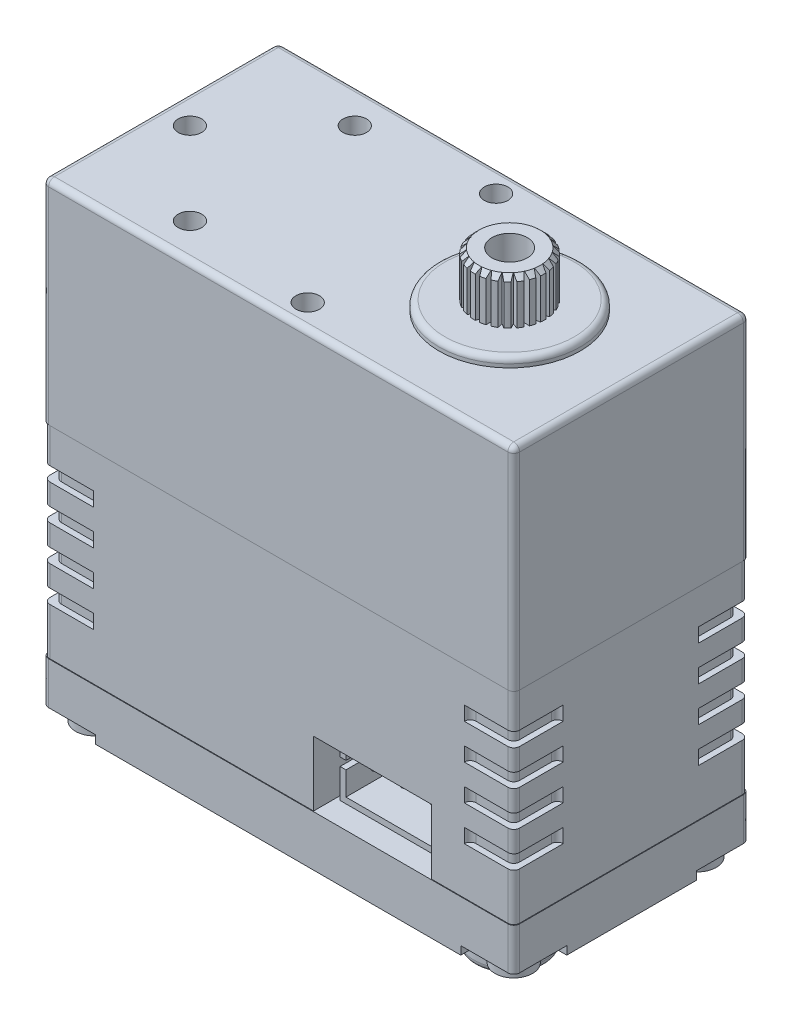
SolidWorks part; units mm, degrees
ref_plane "前视基准面" through (0, 0, 0) normal (0, 0, 1) x (1, 0, 0)
ref_plane "上视基准面" through (0, 0, 0) normal (0, 1, 0) x (1, 0, 0)
ref_plane "右视基准面" through (0, 0, 0) normal (1, 0, 0) x (0, 0, -1)
sketch "草图1" plane through (0, 0, 0) normal (0, 1, 0) x (1, 0, 0)
  line L1 (20, -10) -> (-20, -10)
  line L2 (20, -10) -> (20, 10)
  line L3 (20, 10) -> (-20, 10)
  line L4 (-20, -10) -> (-20, 10)
  line L5 (20, -10) -> (-20, 10) construction
  line L6 (20, 10) -> (-20, -10) construction
  point P0 (0, 0)
  dimension "D1" = 20
  dimension "D2" = 40
extrude "凸台-拉伸1" add sketch "草图1" along normal blind 40
sketch "草图2" plane through (0, 0, 10) normal (0, 0, 1) x (1, 0, 0)
  line L0 (-20, 40) -> (-20, 0) construction
  line L1 (-20, 22) -> (20, 22)
  line L2 (-20, 22) -> (-20, 4.8)
  line L3 (-20, 4.8) -> (20, 4.8)
  line L4 (20, 22) -> (20, 4.8)
  line L5 (20, 40) -> (20, 0) construction
  line L6 (-20, 40) -> (20, 40) construction
  dimension "D1" = 17.2
  dimension "D2" = 18
extrude "切除-拉伸1" cut sketch "草图2" against normal blind 0.05
sketch "草图3" plane through (20, 0, 0) normal (1, 0, 0) x (0, 0, -1)
  line L0 (10, 40) -> (10, 0) construction
  line L1 (-9.95, 22) -> (10, 22)
  line L2 (-9.95, 22) -> (-9.95, 4.8)
  line L3 (-9.95, 4.8) -> (10, 4.8)
  line L4 (10, 22) -> (10, 4.8)
  dimension "D1" = 17.2
extrude "切除-拉伸2" cut sketch "草图3" against normal blind 0.05
sketch "草图4" plane through (0, 0, -10) normal (0, 0, -1) x (-1, 0, 0)
  line L0 (20, 40) -> (20, 0) construction
  line L1 (-19.95, 22) -> (20, 22)
  line L2 (-19.95, 22) -> (-19.95, 4.8)
  line L3 (-19.95, 4.8) -> (20, 4.8)
  line L4 (20, 22) -> (20, 4.8)
  dimension "D1" = 17.2
extrude "切除-拉伸3" cut sketch "草图4" against normal blind 0.05
sketch "草图5" plane through (-20, 0, 0) normal (-1, 0, 0) x (0, 0, 1)
  line L1 (-9.95, 22) -> (10, 22)
  line L2 (-9.95, 22) -> (-9.95, 4.8)
  line L3 (-9.95, 4.8) -> (10, 4.8)
  line L4 (10, 22) -> (10, 4.8)
extrude "切除-拉伸4" cut sketch "草图5" against normal blind 0.05
sketch "草图6" plane through (0, 0, -9.95) normal (0, 0, -1) x (-1, 0, 0)
  line L0 (19.95, 22) -> (19.95, 4.8) construction
  line L1 (15.75, 19) -> (19.95, 19)
  line L2 (15.75, 19) -> (15.75, 17.8)
  line L3 (15.75, 17.8) -> (19.95, 17.8)
  line L4 (19.95, 19) -> (19.95, 17.8)
  line L5 (0, 22) -> (0, 4.8) construction
  line L6 (20, 22) -> (-20, 22) construction
  line L7 (20, 4.8) -> (-20, 4.8) construction
  line L8 (19.95, 22) -> (-19.95, 22) construction
  line L9 (15.75, 16) -> (15.75, 14.8)
  line L10 (15.75, 16) -> (19.95, 16)
  line L11 (19.95, 16) -> (19.95, 14.8)
  line L12 (15.75, 14.8) -> (19.95, 14.8)
  line L13 (15.75, 13) -> (15.75, 11.8)
  line L14 (15.75, 13) -> (19.95, 13)
  line L15 (19.95, 13) -> (19.95, 11.8)
  line L16 (15.75, 11.8) -> (19.95, 11.8)
  line L17 (15.75, 10) -> (15.75, 8.8)
  line L18 (15.75, 10) -> (19.95, 10)
  line L19 (19.95, 10) -> (19.95, 8.8)
  line L20 (15.75, 8.8) -> (19.95, 8.8)
  line L21 (-15.75, 10) -> (-19.95, 10)
  line L22 (-19.95, 10) -> (-19.95, 8.8)
  line L23 (-15.75, 8.8) -> (-19.95, 8.8)
  line L24 (-15.75, 10) -> (-15.75, 8.8)
  line L25 (-15.75, 13) -> (-19.95, 13)
  line L26 (-19.95, 13) -> (-19.95, 11.8)
  line L27 (-15.75, 11.8) -> (-19.95, 11.8)
  line L28 (-15.75, 13) -> (-15.75, 11.8)
  line L29 (-15.75, 16) -> (-19.95, 16)
  line L30 (-19.95, 16) -> (-19.95, 14.8)
  line L31 (-15.75, 14.8) -> (-19.95, 14.8)
  line L32 (-15.75, 16) -> (-15.75, 14.8)
  line L33 (-15.75, 17.8) -> (-19.95, 17.8)
  line L34 (-19.95, 19) -> (-19.95, 17.8)
  line L35 (-15.75, 19) -> (-19.95, 19)
  line L36 (-15.75, 19) -> (-15.75, 17.8)
  dimension "D1" = 3
  dimension "D2" = 1.2
  dimension "D3" = 4.2
  dimension "D4" = 4
extrude "切除-拉伸5" cut sketch "草图6" against normal blind 0.5
sketch "草图7" plane through (-19.95, 0, 0) normal (-1, 0, 0) x (0, 0, 1)
  line L0 (-9.95, 16) -> (-9.95, 14.8)
  line L1 (-9.95, 19) -> (-5.75, 19)
  line L2 (-9.95, 19) -> (-9.95, 17.8)
  line L3 (-9.95, 17.8) -> (-5.75, 17.8)
  line L4 (-5.75, 19) -> (-5.75, 17.8)
  line L5 (-9.95, 16) -> (-5.75, 16)
  line L6 (-5.75, 16) -> (-5.75, 14.8)
  line L7 (-9.95, 14.8) -> (-5.75, 14.8)
  line L8 (-9.95, 13) -> (-9.95, 11.8)
  line L9 (-9.95, 13) -> (-5.75, 13)
  line L10 (-5.75, 13) -> (-5.75, 11.8)
  line L11 (-9.95, 11.8) -> (-5.75, 11.8)
  line L12 (-9.95, 10) -> (-9.95, 8.8)
  line L13 (-9.95, 10) -> (-5.75, 10)
  line L14 (-5.75, 10) -> (-5.75, 8.8)
  line L15 (-9.95, 8.8) -> (-5.75, 8.8)
  line L16 (0, 22) -> (0, 4.8) construction
  line L17 (-10, 22) -> (10, 22) construction
  line L18 (-10, 4.8) -> (10, 4.8) construction
  line L19 (9.95, 10) -> (5.75, 10)
  line L20 (5.75, 10) -> (5.75, 8.8)
  line L21 (9.95, 8.8) -> (5.75, 8.8)
  line L22 (9.95, 10) -> (9.95, 8.8)
  line L23 (9.95, 13) -> (5.75, 13)
  line L24 (5.75, 13) -> (5.75, 11.8)
  line L25 (9.95, 11.8) -> (5.75, 11.8)
  line L26 (9.95, 13) -> (9.95, 11.8)
  line L27 (9.95, 16) -> (5.75, 16)
  line L28 (5.75, 16) -> (5.75, 14.8)
  line L29 (9.95, 14.8) -> (5.75, 14.8)
  line L30 (9.95, 16) -> (9.95, 14.8)
  line L31 (9.95, 17.8) -> (5.75, 17.8)
  line L32 (5.75, 19) -> (5.75, 17.8)
  line L33 (9.95, 19) -> (5.75, 19)
  line L34 (9.95, 19) -> (9.95, 17.8)
  dimension "D1" = 4.2
  dimension "D2" = 1.2
  dimension "D3" = 4
extrude "切除-拉伸6" cut sketch "草图7" against normal blind 0.5
sketch "草图8" plane through (0, 0, 9.95) normal (0, 0, 1) x (1, 0, 0)
  line L0 (0, 22) -> (0, 4.8) construction
  line L1 (-19.95, 19) -> (-15.75, 19)
  line L2 (-19.95, 19) -> (-19.95, 17.8)
  line L3 (-19.95, 17.8) -> (-15.75, 17.8)
  line L4 (-15.75, 19) -> (-15.75, 17.8)
  line L5 (20, 22) -> (-20, 22) construction
  line L6 (-20, 4.8) -> (20, 4.8) construction
  line L7 (-19.95, 16) -> (-19.95, 14.8)
  line L8 (-19.95, 16) -> (-15.75, 16)
  line L9 (-15.75, 16) -> (-15.75, 14.8)
  line L10 (-19.95, 14.8) -> (-15.75, 14.8)
  line L11 (-19.95, 13) -> (-19.95, 11.8)
  line L12 (-19.95, 13) -> (-15.75, 13)
  line L13 (-15.75, 13) -> (-15.75, 11.8)
  line L14 (-19.95, 11.8) -> (-15.75, 11.8)
  line L15 (-19.95, 10) -> (-19.95, 8.8)
  line L16 (-19.95, 10) -> (-15.75, 10)
  line L17 (-15.75, 10) -> (-15.75, 8.8)
  line L18 (-19.95, 8.8) -> (-15.75, 8.8)
  line L19 (19.95, 10) -> (15.75, 10)
  line L20 (15.75, 10) -> (15.75, 8.8)
  line L21 (19.95, 8.8) -> (15.75, 8.8)
  line L22 (19.95, 10) -> (19.95, 8.8)
  line L23 (19.95, 13) -> (15.75, 13)
  line L24 (15.75, 13) -> (15.75, 11.8)
  line L25 (19.95, 11.8) -> (15.75, 11.8)
  line L26 (19.95, 13) -> (19.95, 11.8)
  line L27 (19.95, 16) -> (15.75, 16)
  line L28 (15.75, 16) -> (15.75, 14.8)
  line L29 (19.95, 14.8) -> (15.75, 14.8)
  line L30 (19.95, 16) -> (19.95, 14.8)
  line L31 (19.95, 17.8) -> (15.75, 17.8)
  line L32 (15.75, 19) -> (15.75, 17.8)
  line L33 (19.95, 19) -> (15.75, 19)
  line L34 (19.95, 19) -> (19.95, 17.8)
  dimension "D1" = 1.2
  dimension "D2" = 4.2
  dimension "D3" = 4
extrude "切除-拉伸7" cut sketch "草图8" against normal blind 0.5
sketch "草图9" plane through (19.95, 0, 0) normal (1, 0, 0) x (0, 0, -1)
  line L0 (0, 22) -> (0, 4.8) construction
  line L1 (-9.95, 19) -> (-5.75, 19)
  line L2 (-9.95, 19) -> (-9.95, 17.8)
  line L3 (-9.95, 17.8) -> (-5.75, 17.8)
  line L4 (-5.75, 19) -> (-5.75, 17.8)
  line L5 (10, 22) -> (-10, 22) construction
  line L6 (10, 4.8) -> (-10, 4.8) construction
  line L7 (-9.95, 16) -> (-9.95, 14.8)
  line L8 (-9.95, 16) -> (-5.75, 16)
  line L9 (-5.75, 16) -> (-5.75, 14.8)
  line L10 (-9.95, 14.8) -> (-5.75, 14.8)
  line L11 (-9.95, 13) -> (-9.95, 11.8)
  line L12 (-9.95, 13) -> (-5.75, 13)
  line L13 (-5.75, 13) -> (-5.75, 11.8)
  line L14 (-9.95, 11.8) -> (-5.75, 11.8)
  line L15 (-9.95, 10) -> (-9.95, 8.8)
  line L16 (-9.95, 10) -> (-5.75, 10)
  line L17 (-5.75, 10) -> (-5.75, 8.8)
  line L18 (-9.95, 8.8) -> (-5.75, 8.8)
  line L19 (9.95, 10) -> (5.75, 10)
  line L20 (5.75, 10) -> (5.75, 8.8)
  line L21 (9.95, 8.8) -> (5.75, 8.8)
  line L22 (9.95, 10) -> (9.95, 8.8)
  line L23 (9.95, 13) -> (5.75, 13)
  line L24 (5.75, 13) -> (5.75, 11.8)
  line L25 (9.95, 11.8) -> (5.75, 11.8)
  line L26 (9.95, 13) -> (9.95, 11.8)
  line L27 (9.95, 16) -> (5.75, 16)
  line L28 (5.75, 16) -> (5.75, 14.8)
  line L29 (9.95, 14.8) -> (5.75, 14.8)
  line L30 (9.95, 16) -> (9.95, 14.8)
  line L31 (9.95, 17.8) -> (5.75, 17.8)
  line L32 (5.75, 19) -> (5.75, 17.8)
  line L33 (9.95, 19) -> (5.75, 19)
  line L34 (9.95, 19) -> (9.95, 17.8)
  dimension "D1" = 1.2
  dimension "D2" = 4.2
  dimension "D3" = 4
extrude "切除-拉伸8" cut sketch "草图9" against normal blind 0.5
sketch "草图10" plane through (0, 0, 0) normal (0, -1, 0) x (1, 0, 0)
  line L0 (-20, 0) -> (20, 0) construction
  line L1 (-20, -10) -> (-20, 10) construction
  line L2 (20, 10) -> (20, -10) construction
  line L3 (0, 10) -> (0, -10) construction
  line L4 (-20, 10) -> (20, 10) construction
  line L5 (20, -10) -> (-20, -10) construction
  line L6 (-20, -5.5) -> (-19, -5.5)
  line L7 (-20, 10) -> (-15.5, 10)
  line L8 (-20, 10) -> (-20, 5.5)
  line L9 (-20, 5.5) -> (-19, 5.5)
  line L10 (-15.5, 10) -> (-15.5, 9)
  line L11 (-15.5, -10) -> (-15.5, -9)
  line L12 (-20, -10) -> (-15.5, -10)
  line L13 (-20, -10) -> (-20, -5.5)
  line L14 (20, -10) -> (20, -5.5)
  line L15 (20, -10) -> (15.5, -10)
  line L16 (15.5, -10) -> (15.5, -9)
  line L17 (20, -5.5) -> (19, -5.5)
  line L18 (20, 5.5) -> (19, 5.5)
  line L19 (15.5, 10) -> (15.5, 9)
  line L20 (20, 10) -> (15.5, 10)
  line L21 (20, 10) -> (20, 5.5)
  arc A0 (-19, 5.5) -> (-15.5, 9) centre (-19, 9) ccw
  arc A1 (-19, -5.5) -> (-15.5, -9) centre (-19, -9) cw
  arc A2 (19, -5.5) -> (15.5, -9) centre (19, -9) ccw
  arc A3 (19, 5.5) -> (15.5, 9) centre (19, 9) cw
  dimension "D3" = 3.5
  dimension "D1" = 4.5
  dimension "D2" = 4.5
extrude "切除-拉伸9" cut sketch "草图10" against normal blind 1.2
fillet "圆角1" radius 0.5 80 edges at (20, 3, 10) (19.95, 6.8, 9.95) (19.45, 9.4, 9.45) (19.95, 10.9, 9.95) (19.45, 12.4, 9.45) (19.95, 13.9, 9.95) (19.45, 15.4, 9.45) (19.95, 16.9, 9.95) (19.45, 18.4, 9.45) (20, 31, 10) (19.95, 20.5, 9.95) (-20, 3, 10) (-19.95, 6.8, 9.95) (-19.45, 9.4, 9.45) (-19.95, 10.9, 9.95) (-19.45, 12.4, 9.45) (-19.95, 13.9, 9.95) (-19.45, 15.4, 9.45) (-19.95, 16.9, 9.95) (-19.45, 18.4, 9.45) (-20, 31, 10) (-19.95, 20.5, 9.95) (-20, 3, -10) (-19.95, 6.8, -9.95) (-19.45, 9.4, -9.45) (-19.95, 10.9, -9.95) (-19.45, 12.4, -9.45) (-19.95, 13.9, -9.95) (-19.45, 15.4, -9.45) (-19.95, 16.9, -9.95) (-19.45, 18.4, -9.45) (-20, 31, -10) (-19.95, 20.5, -9.95) (-20, 40, 0) (0, 40, 10) (20, 40, 0) (20, 3, -10) (19.95, 6.8, -9.95) (19.45, 9.4, -9.45) (19.95, 10.9, -9.95) (19.45, 12.4, -9.45) (19.95, 13.9, -9.95) (19.95, 16.9, -9.95) (19.45, 15.4, -9.45) (19.45, 18.4, -9.45) (20, 31, -10) (19.95, 20.5, -9.95) (0, 40, -10) (19.45, 9.4, 5.75) (19.45, 12.4, 5.75) (19.45, 15.4, 5.75) (19.45, 18.4, 5.75) (15.75, 9.4, 9.45) (15.75, 12.4, 9.45) (15.75, 15.4, 9.45) (15.75, 18.4, 9.45) (19.45, 18.4, -5.75) (19.45, 15.4, -5.75) (19.45, 12.4, -5.75) (19.45, 9.4, -5.75) (15.75, 9.4, -9.45) (15.75, 12.4, -9.45) (15.75, 15.4, -9.45) (15.75, 18.4, -9.45) (-15.75, 9.4, -9.45) (-15.75, 12.4, -9.45) (-15.75, 15.4, -9.45) (-15.75, 18.4, -9.45) (-19.45, 9.4, -5.75) (-19.45, 12.4, -5.75) (-19.45, 15.4, -5.75) (-19.45, 18.4, -5.75) (-15.75, 9.4, 9.45) (-15.75, 12.4, 9.45) (-15.75, 15.4, 9.45) (-15.75, 18.4, 9.45) (-19.45, 9.4, 5.75) (-19.45, 12.4, 5.75) (-19.45, 15.4, 5.75) (-19.45, 18.4, 5.75)
chamfer "倒角1" distance 0.5 angle 45 16 edges at (19.5, 0, -5.5) (16.5251, 0, -6.5251) (15.5, 0, -9.5) (0, 0, -10) (-15.5, 0, -9.5) (-16.5251, 0, -6.5251) (-19.5, 0, -5.5) (-20, 0, 0) (-19.5, 0, 5.5) (-16.5251, 0, 6.5251) (-15.5, 0, 9.5) (0, 0, 10) (15.5, 0, 9.5) (16.5251, 0, 6.5251) (19.5, 0, 5.5) (20, 0, 0)
sketch "草图12" plane through (0, 1.2, 0) normal (0, -1, 0) x (1, 0, 0)
  line L0 (-15.5, 10) -> (-19.5, 10) construction
  line L1 (-20, 9.5) -> (-20, 5.5) construction
  line L2 (-20, 0) -> (20, 0) construction
  line L3 (-20, -5.5) -> (-20, 5.5) construction
  line L4 (20, 5.5) -> (20, -5.5) construction
  line L5 (0, 10) -> (0, -10) construction
  line L6 (-15.5, 10) -> (15.5, 10) construction
  line L7 (15.5, -10) -> (-15.5, -10) construction
  circle A0 centre (-17.8, 7.8) radius 1.6
  circle A2 centre (-17.8, -7.8) radius 1.6
  circle A3 centre (17.8, -7.8) radius 1.6
  circle A4 centre (17.8, 7.8) radius 1.6
  dimension "D3" = 3.2
  dimension "D1" = 2.2
  dimension "D2" = 2.2
extrude "凸台-拉伸2" add sketch "草图12" along normal blind 1.2
sketch "草图13" plane through (0, 0, 0) normal (0, -1, 0) x (1, 0, 0)
  line L0 (-20, 0) -> (20, 0) construction
  line L1 (-20, -5.5) -> (-20, 5.5) construction
  line L2 (20, 5.5) -> (20, -5.5) construction
  line L3 (0, 10) -> (0, -10) construction
  line L4 (-15.5, 10) -> (15.5, 10) construction
  line L5 (15.5, -10) -> (-15.5, -10) construction
  line L6 (-18.3, 8.666) -> (-17.3, 8.666)
  line L7 (-17.3, 8.666) -> (-16.8, 7.8)
  line L8 (-16.8, 7.8) -> (-17.3, 6.934)
  line L9 (-17.3, 6.934) -> (-18.3, 6.934)
  line L10 (-18.3, 6.934) -> (-18.8, 7.8)
  line L11 (-18.8, 7.8) -> (-18.3, 8.666)
  line L12 (-18.3, -6.934) -> (-18.8, -7.8)
  line L13 (-17.3, -6.934) -> (-18.3, -6.934)
  line L14 (-16.8, -7.8) -> (-17.3, -6.934)
  line L15 (-17.3, -8.666) -> (-16.8, -7.8)
  line L16 (-18.3, -8.666) -> (-17.3, -8.666)
  line L17 (-18.8, -7.8) -> (-18.3, -8.666)
  line L18 (17.3, -6.934) -> (18.3, -6.934)
  line L19 (16.8, -7.8) -> (17.3, -6.934)
  line L20 (17.3, -8.666) -> (16.8, -7.8)
  line L21 (18.3, -8.666) -> (17.3, -8.666)
  line L22 (18.8, -7.8) -> (18.3, -8.666)
  line L23 (18.3, -6.934) -> (18.8, -7.8)
  line L24 (18.3, 6.934) -> (18.8, 7.8)
  line L25 (17.3, 6.934) -> (18.3, 6.934)
  line L26 (16.8, 7.8) -> (17.3, 6.934)
  line L27 (17.3, 8.666) -> (16.8, 7.8)
  line L28 (18.3, 8.666) -> (17.3, 8.666)
  line L29 (18.8, 7.8) -> (18.3, 8.666)
  circle A4 centre (-17.8, 7.8) radius 1.6 construction
  circle A5 centre (-17.8, 7.8) radius 1.6 construction
  point P18 (-17.8, 8.666)
  dimension "D1" = 120
  dimension "D2" = 120
  dimension "D3" = 120
  dimension "D4" = 1
  dimension "D5" = 1
  dimension "D6" = 1
  dimension "D7" = 1
extrude "切除-拉伸10" cut sketch "草图13" against normal blind 0.5
sketch "草图14" plane through (0, 40, 0) normal (0, 1, 0) x (1, 0, 0)
  line L0 (-19.5, 0) -> (19.5, 0) construction
  line L1 (-19.5, 9.5) -> (-19.5, -9.5) construction
  line L2 (19.5, -9.5) -> (19.5, 9.5) construction
  line L3 (0, 9.5) -> (0, -9.5) construction
  line L4 (19.5, 9.5) -> (-19.5, 9.5) construction
  line L5 (-19.5, -9.5) -> (19.5, -9.5) construction
  line L6 (-20, -9.5) -> (-20, 9.5) construction
  circle A0 centre (9.65, 0) radius 6
  dimension "D1" = 12
  dimension "D2" = 29.65
extrude "凸台-拉伸3" add sketch "草图14" along normal blind 0.8
sketch "草图15" plane through (0, 40.8, 0) normal (0, 1, 0) x (1, 0, 0)
  circle A0 centre (9.65, 0) radius 3
  dimension "D1" = 6
extrude "凸台-拉伸4" add sketch "草图15" along normal blind 3.8
sketch "草图16" plane through (0, 44.6, 0) normal (0, 1, 0) x (1, 0, 0)
  line L0 (9.2204, 2.9691) -> (9.4285, 2.5623)
  line L1 (9.4285, 2.5623) -> (9.5696, 2.9989)
  line L2 (10.0992, 2.5323) -> (10.3485, 2.9176)
  line L3 (10.0035, 2.9791) -> (10.0992, 2.5323)
  line L4 (10.7393, 2.3297) -> (11.0798, 2.6374)
  line L5 (10.7625, 2.7861) -> (10.7393, 2.3297)
  line L6 (11.3052, 1.9684) -> (11.7137, 2.1774)
  line L7 (11.4457, 2.4032) -> (11.3052, 1.9684)
  line L8 (11.7583, 1.4729) -> (12.2069, 1.5691)
  line L9 (12.0065, 1.8566) -> (11.7583, 1.4729)
  line L10 (12.0677, 0.8771) -> (12.5259, 0.8539)
  line L11 (12.4067, 1.1834) -> (12.0677, 0.8771)
  line L12 (12.2123, 0.2215) -> (12.6489, 0.0804)
  line L13 (12.6191, 0.4296) -> (12.2123, 0.2215)
  line L14 (12.1823, -0.4492) -> (12.5676, -0.6985)
  line L15 (12.6291, -0.3535) -> (12.1823, -0.4492)
  line L16 (11.9797, -1.0893) -> (12.2874, -1.4298)
  line L17 (12.4361, -1.1125) -> (11.9797, -1.0893)
  line L18 (11.6184, -1.6552) -> (11.8274, -2.0637)
  line L19 (12.0532, -1.7957) -> (11.6184, -1.6552)
  line L20 (11.1229, -2.1083) -> (11.2191, -2.5569)
  line L21 (11.5066, -2.3565) -> (11.1229, -2.1083)
  line L22 (10.5271, -2.4177) -> (10.5039, -2.8759)
  line L23 (10.8334, -2.7567) -> (10.5271, -2.4177)
  line L24 (9.8715, -2.5623) -> (9.7304, -2.9989)
  line L25 (10.0796, -2.9691) -> (9.8715, -2.5623)
  line L26 (9.2008, -2.5323) -> (8.9515, -2.9176)
  line L27 (9.2965, -2.9791) -> (9.2008, -2.5323)
  line L28 (8.5607, -2.3297) -> (8.2202, -2.6374)
  line L29 (8.5375, -2.7861) -> (8.5607, -2.3297)
  line L30 (7.9948, -1.9684) -> (7.5863, -2.1774)
  line L31 (7.8543, -2.4032) -> (7.9948, -1.9684)
  line L32 (7.5417, -1.4729) -> (7.0931, -1.5691)
  line L33 (7.2935, -1.8566) -> (7.5417, -1.4729)
  line L34 (7.2323, -0.8771) -> (6.7741, -0.8539)
  line L35 (6.8933, -1.1834) -> (7.2323, -0.8771)
  line L36 (7.0877, -0.2215) -> (6.6511, -0.0804)
  line L37 (6.6809, -0.4296) -> (7.0877, -0.2215)
  line L38 (7.1177, 0.4492) -> (6.7324, 0.6985)
  line L39 (6.6709, 0.3535) -> (7.1177, 0.4492)
  line L40 (7.3203, 1.0893) -> (7.0126, 1.4298)
  line L41 (6.8639, 1.1125) -> (7.3203, 1.0893)
  line L42 (7.6816, 1.6552) -> (7.4726, 2.0637)
  line L43 (7.2468, 1.7957) -> (7.6816, 1.6552)
  line L44 (8.1771, 2.1083) -> (8.0809, 2.5569)
  line L45 (7.7934, 2.3565) -> (8.1771, 2.1083)
  line L46 (8.7729, 2.4177) -> (8.7961, 2.8759)
  line L47 (8.4666, 2.7567) -> (8.7729, 2.4177)
  line L48 (20, 9.5) -> (20, -9.5) construction
  arc A0 (8.0809, 2.5569) -> (7.7934, 2.3565) centre (9.65, 0) ccw
  arc A1 (8.7961, 2.8759) -> (8.4666, 2.7567) centre (9.65, 0) ccw
  arc A2 (9.5696, 2.9989) -> (9.2204, 2.9691) centre (9.65, 0) ccw
  arc A3 (10.3485, 2.9176) -> (10.0035, 2.9791) centre (9.65, 0) ccw
  arc A4 (11.0798, 2.6374) -> (10.7625, 2.7861) centre (9.65, 0) ccw
  arc A5 (11.7137, 2.1774) -> (11.4457, 2.4032) centre (9.65, 0) ccw
  arc A6 (12.2069, 1.5691) -> (12.0065, 1.8566) centre (9.65, 0) ccw
  arc A7 (12.5259, 0.8539) -> (12.4067, 1.1834) centre (9.65, 0) ccw
  arc A8 (12.6489, 0.0804) -> (12.6191, 0.4296) centre (9.65, 0) ccw
  arc A9 (12.5676, -0.6985) -> (12.6291, -0.3535) centre (9.65, 0) ccw
  arc A10 (12.2874, -1.4298) -> (12.4361, -1.1125) centre (9.65, 0) ccw
  arc A11 (11.8274, -2.0637) -> (12.0532, -1.7957) centre (9.65, 0) ccw
  arc A12 (11.2191, -2.5569) -> (11.5066, -2.3565) centre (9.65, 0) ccw
  arc A13 (10.5039, -2.8759) -> (10.8334, -2.7567) centre (9.65, 0) ccw
  arc A14 (9.7304, -2.9989) -> (10.0796, -2.9691) centre (9.65, 0) ccw
  arc A15 (8.9515, -2.9176) -> (9.2965, -2.9791) centre (9.65, 0) ccw
  arc A16 (8.2202, -2.6374) -> (8.5375, -2.7861) centre (9.65, 0) ccw
  arc A17 (7.5863, -2.1774) -> (7.8543, -2.4032) centre (9.65, 0) ccw
  arc A18 (7.0931, -1.5691) -> (7.2935, -1.8566) centre (9.65, 0) ccw
  arc A19 (6.7741, -0.8539) -> (6.8933, -1.1834) centre (9.65, 0) ccw
  arc A20 (6.6511, -0.0804) -> (6.6809, -0.4296) centre (9.65, 0) ccw
  arc A21 (6.7324, 0.6985) -> (6.6709, 0.3535) centre (9.65, 0) ccw
  arc A22 (7.0126, 1.4298) -> (6.8639, 1.1125) centre (9.65, 0) ccw
  arc A23 (7.4726, 2.0637) -> (7.2468, 1.7957) centre (9.65, 0) ccw
  circle A24 centre (9.65, 0) radius 1.5
  point P78 (9.65, 0)
  dimension "D3" = 3
  dimension "D2" = 45
  dimension "D1" = 24
extrude "切除-拉伸11" cut sketch "草图16" against normal up to surface (3.8 mm away) up to face at (9.65, 40.8, 3)
sketch "草图17" plane through (0, 40, 0) normal (0, 1, 0) x (1, 0, 0)
  line L0 (-19.5, 0) -> (19.5, 0) construction
  line L1 (-19.5, 9.5) -> (-19.5, -9.5) construction
  line L2 (19.5, -9.5) -> (19.5, 9.5) construction
  line L3 (-20, -9.5) -> (-20, 9.5) construction
  circle A0 centre (-17.5, 0) radius 1
  circle A1 centre (0.5, 8) radius 1
  circle A2 centre (-10.5, 7) radius 1
  circle A3 centre (0.5, -8) radius 1
  circle A4 centre (-10.5, -7) radius 1
  dimension "D1" = 2
  dimension "D2" = 2
  dimension "D4" = 2
  dimension "D3" = 20.5
  dimension "D5" = 9.5
  dimension "D6" = 2.5
  dimension "D7" = 8
  dimension "D8" = 7
extrude "切除-拉伸12" cut sketch "草图17" against normal blind 4.5
ref_plane "基准面1" through (0, 20, 0) normal (0, 1, 0) x (1, 0, 0)
mirror "镜向1" about plane through (0, 20, 0) normal (0, 1, 0) of "切除-拉伸12"
fillet "圆角2" radius 0.5 1 edges at (9.65, 40.8, 6)
chamfer "倒角2" distance 0.4 angle 45 24 edges at (6.6531, 44.6, -0.1369) (6.7198, 44.6, 0.6434) (6.9862, 44.6, 1.3799) (7.4341, 44.6, 2.0223) (8.033, 44.6, 2.5269) (8.7421, 44.6, 2.8593) (9.5131, 44.6, 2.9969) (10.2934, 44.6, 2.9302) (11.0299, 44.6, 2.6638) (11.6723, 44.6, 2.2159) (12.1769, 44.6, 1.617) (12.5093, 44.6, 0.9079) (12.6469, 44.6, 0.1369) (11.8659, 44.6, -2.0223) (12.3138, 44.6, -1.3799) (12.5802, 44.6, -0.6434) (6.7907, 44.6, -0.9079) (7.1231, 44.6, -1.617) (7.6277, 44.6, -2.2159) (8.2701, 44.6, -2.6638) (9.0066, 44.6, -2.9302) (9.7869, 44.6, -2.9969) (10.5579, 44.6, -2.8593) (11.267, 44.6, -2.5269)
mirror "镜向2" about plane through (0, 20, 0) normal (0, 1, 0) of "圆角2", "凸台-拉伸3"
sketch "草图18" plane through (0, -0.8, 0) normal (0, -1, 0) x (1, 0, 0)
  circle A0 centre (9.65, 0) radius 3
  dimension "D1" = 6
extrude "凸台-拉伸5" add sketch "草图18" along normal blind 6
fillet "圆角4" radius 0.5 1 edges at (9.65, -6.8, -3)
sketch "草图19" plane through (0, 0, 9.95) normal (0, 0, 1) x (1, 0, 0)
  line L0 (-19.5, 4.8) -> (19.5, 4.8) construction
  line L1 (2.95, 4.8) -> (12.95, 4.8)
  line L2 (2.95, 4.8) -> (2.95, 10.3)
  line L3 (2.95, 10.3) -> (12.95, 10.3)
  line L4 (12.95, 4.8) -> (12.95, 10.3)
  line L5 (19.95, 8.8) -> (19.95, 4.8) construction
  dimension "D1" = 5.5
  dimension "D2" = 10
  dimension "D3" = 7
extrude "切除-拉伸13" cut sketch "草图19" against normal blind 6
sketch "草图20" plane through (0, 0, 3.95) normal (0, 0, 1) x (1, 0, 0)
  line L0 (3.7, 9.9) -> (12.2, 9.9)
  line L1 (12.2, 9.9) -> (12.2, 8.4)
  line L2 (12.2, 8.4) -> (11.7, 8.4)
  line L3 (11.7, 8.4) -> (11.7, 8.9)
  line L4 (11.7, 8.9) -> (8.7, 8.9)
  line L5 (8.7, 8.9) -> (8.7, 9.4)
  line L6 (8.7, 9.4) -> (7.2, 9.4)
  line L7 (7.2, 9.4) -> (7.2, 8.9)
  line L8 (7.2, 8.9) -> (4.2, 8.9)
  line L9 (4.2, 8.9) -> (4.2, 8.4)
  line L10 (4.2, 8.4) -> (3.7, 8.4)
  line L11 (3.7, 8.4) -> (3.7, 9.9)
  line L12 (12.2, 7.7) -> (12.2, 5.2)
  line L13 (12.2, 5.2) -> (3.7, 5.2)
  line L14 (3.7, 5.2) -> (3.7, 7.7)
  line L15 (3.7, 7.7) -> (4.2, 7.7)
  line L16 (4.2, 7.7) -> (4.2, 5.7)
  line L17 (4.2, 5.7) -> (11.7, 5.7)
  line L18 (11.7, 5.7) -> (11.7, 7.7)
  line L19 (11.7, 7.7) -> (12.2, 7.7)
  line L20 (12.95, 4.8) -> (12.95, 10.3) construction
  line L21 (2.95, 4.8) -> (12.95, 4.8) construction
  point P23 (11.95, 8.4)
  dimension "D1" = 0.5
  dimension "D2" = 0.5
  dimension "D3" = 0.5
  dimension "D4" = 0.5
  dimension "D5" = 0.5
  dimension "D6" = 1
  dimension "D7" = 1
  dimension "D8" = 2.5
  dimension "D9" = 1.5
  dimension "D10" = 1.5
  dimension "D11" = 2.5
  dimension "D12" = 8.5
  dimension "D13" = 0.75
  dimension "D14" = 0.7
  dimension "D15" = 0.4
  dimension "D16" = 1.5
  dimension "D17" = 3.5
extrude "凸台-拉伸6" add sketch "草图20" along normal blind 4.5
sketch "草图21" plane through (0, 0, 3.95) normal (0, 0, 1) x (1, 0, 0)
  line L0 (7.95, 10.3) -> (7.95, 4.8) construction
  line L1 (12.95, 10.3) -> (2.95, 10.3) construction
  line L2 (2.95, 4.8) -> (12.95, 4.8) construction
  circle A0 centre (7.95, 8) radius 0.25
  circle A1 centre (10.45, 8) radius 0.25
  circle A2 centre (5.45, 8) radius 0.25
  dimension "D1" = 0.5
  dimension "D4" = 2.3
  dimension "D2" = 2
  dimension "D3" = 2
extrude "凸台-拉伸7" add sketch "草图21" along normal blind 3.5
mirror "镜向3" about plane through (0, 0, 0) normal (0, 0, 1) of "切除-拉伸13", "凸台-拉伸6", "凸台-拉伸7"
